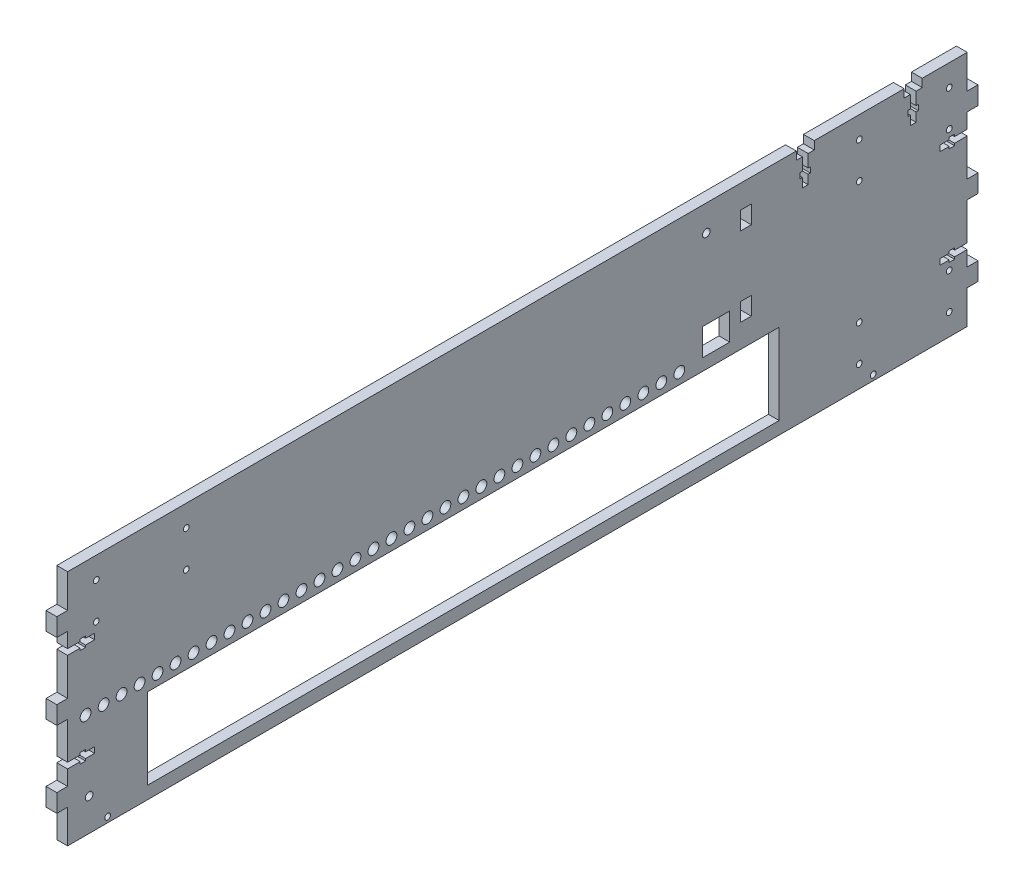
SolidWorks part; units mm, degrees
ref_plane "Front Plane" through (0, 0, 0) normal (0, 0, 1) x (1, 0, 0)
ref_plane "Top Plane" through (0, 0, 0) normal (0, 1, 0) x (1, 0, 0)
ref_plane "Right Plane" through (0, 0, 0) normal (1, 0, 0) x (0, 0, -1)
sketch "Sketch1" plane through (0, 0, 0) normal (1, 0, 0) x (0, 0, -1)
  line L1 (-250, -66) -> (250, -66)
  line L2 (-250, -66) -> (-250, 66)
  line L3 (-250, 66) -> (250, 66)
  line L4 (250, -66) -> (250, 66)
  line L5 (-250, -66) -> (250, 66) construction
  line L6 (-250, 66) -> (250, -66) construction
  point P0 (0, 0)
  dimension "D1" = 132
  dimension "D2" = 500
extrude "Boss-Extrude1" add sketch "Sketch1" along normal blind 6
sketch "Sketch4" plane through (0, 0, 250) normal (0, 0, 1) x (1, 0, 0)
  line L0 (0, 66) -> (0, -66) construction
  line L1 (0, 47.3321) -> (6, 47.3321)
  line L2 (0, 47.3321) -> (0, 37.3321)
  line L3 (0, 37.3321) -> (6, 37.3321)
  line L4 (6, 47.3321) -> (6, 37.3321)
  line L5 (6, 66) -> (6, -66) construction
  line L6 (0, 37.3321) -> (6, 37.3321) construction
  line L7 (0, -66) -> (0, 66) construction
  line L8 (6, 47.3321) -> (0, 47.3321) construction
  line L9 (0, -5) -> (6, -5) construction
  line L10 (0, -5) -> (6, -5)
  line L11 (0, -5) -> (0, 5)
  line L12 (0, 5) -> (6, 5)
  line L13 (6, -5) -> (6, 5)
  line L14 (6, -66) -> (6, 66) construction
  line L15 (6, 5) -> (0, 5) construction
  line L16 (6, -37.3321) -> (0, -37.3321) construction
  line L17 (0, -47.3321) -> (6, -47.3321)
  line L18 (0, -47.3321) -> (0, -37.3321)
  line L19 (0, -37.3321) -> (6, -37.3321)
  line L20 (6, -47.3321) -> (6, -37.3321)
  line L21 (0, -47.3321) -> (6, -47.3321) construction
extrude "Boss-Extrude2" add sketch "Sketch4" along normal blind 6
sketch "Sketch5" plane through (0, 0, 0) normal (-1, 0, 0) x (0, 0, 1)
  line L1 (250, 28.9321) -> (250, 25.7321) construction
  line L3 (250, 28.9321) -> (250, 25.7321) construction
  line L4 (250, -25.7321) -> (250, -28.9321) construction
  line L5 (250, -25.7321) -> (250, -28.9321) construction
  line L6 (250, 27.3321) -> (235, 27.3321) construction
  line L7 (250, -27.3321) -> (235, -27.3321) construction
  line L8 (250, -25.7321) -> (243, -25.7321)
  line L9 (250, 28.9321) -> (243, 28.9321)
  line L10 (250, -28.9321) -> (243, -28.9321)
  line L11 (250, 25.7321) -> (243, 25.7321)
  line L12 (250, -25.7321) -> (250, -28.9321)
  line L13 (235, -25.7321) -> (235, -28.9321)
  line L14 (250, 28.9321) -> (250, 25.7321)
  line L15 (235, 28.9321) -> (235, 25.7321)
  line L16 (240, 25.7321) -> (235, 25.7321)
  line L17 (243, 24.5321) -> (240, 24.5321)
  line L18 (243, 24.5321) -> (243, 25.7321)
  line L19 (243, 30.1321) -> (240, 30.1321)
  line L20 (240, 24.5321) -> (240, 25.7321)
  line L21 (243, 24.5321) -> (240, 30.1321) construction
  line L22 (243, 30.1321) -> (240, 24.5321) construction
  line L23 (243, -30.1321) -> (240, -30.1321)
  line L24 (243, -30.1321) -> (243, -28.9321)
  line L25 (243, -24.5321) -> (240, -24.5321)
  line L26 (240, -30.1321) -> (240, -28.9321)
  line L27 (243, -30.1321) -> (240, -24.5321) construction
  line L28 (243, -24.5321) -> (240, -30.1321) construction
  line L29 (250, 25.7321) -> (235, 25.7321) construction
  line L30 (243, 28.9321) -> (243, 30.1321)
  line L31 (240, 28.9321) -> (235, 28.9321)
  line L32 (250, 28.9321) -> (235, 28.9321) construction
  line L33 (240, 28.9321) -> (240, 30.1321)
  line L34 (240, -25.7321) -> (235, -25.7321)
  line L35 (250, -25.7321) -> (235, -25.7321) construction
  line L36 (240, -25.7321) -> (240, -24.5321)
  line L37 (240, -28.9321) -> (235, -28.9321)
  line L38 (250, -28.9321) -> (235, -28.9321) construction
  line L39 (243, -25.7321) -> (243, -24.5321)
  point P20 (241.5, 27.3321)
  point P25 (241.5, -27.3321)
  line M35 (250, -37.3321) -> (250, -5)
  line M39 (250, 5) -> (250, 37.3321)
  dimension "D3" = 1.6
  dimension "D4" = 7
  dimension "D5" = 3
  dimension "D6" = 5.6
  dimension "D1" = 15
  dimension "D7" = 7
  dimension "D8" = 3
  dimension "D9" = 5.6
  dimension "D2" = 1.6
extrude "Cut-Extrude3" cut sketch "Sketch5" against normal up to next contours L12 | L8 L39 L25 L36 L34 L13 L37 L26 L23 L24 L10 M35 | L33 L31 L15 L16 L20 L17 L18 L11 L9 L30 L19 M39 region at (0, -27.3321, 242.3696) region at (0, 27.3321, 242.3696)
sketch "Sketch6" plane through (0, 0, -250) normal (0, 0, -1) x (-1, 0, 0)
  line L0 (0, 47.3321) -> (0, 37.3321) construction
  line L1 (0, 37.3321) -> (-6, 37.3321) construction
  line L2 (-6, 37.3321) -> (-6, 47.3321) construction
  line L3 (-6, 47.3321) -> (0, 47.3321) construction
  line L4 (0, 5) -> (0, -5) construction
  line L5 (0, -5) -> (-6, -5) construction
  line L6 (-6, -5) -> (-6, 5) construction
  line L7 (-6, 5) -> (0, 5) construction
  line L8 (0, -37.3321) -> (0, -47.3321) construction
  line L9 (0, -47.3321) -> (-6, -47.3321) construction
  line L10 (-6, -47.3321) -> (-6, -37.3321) construction
  line L11 (-6, -37.3321) -> (0, -37.3321) construction
  line L12 (0, 47.3321) -> (0, 37.3321)
  line L13 (0, 37.3321) -> (-6, 37.3321)
  line L14 (-6, 37.3321) -> (-6, 47.3321)
  line L15 (-6, 47.3321) -> (0, 47.3321)
  line L16 (0, 5) -> (0, -5)
  line L17 (0, -5) -> (-6, -5)
  line L18 (-6, -5) -> (-6, 5)
  line L19 (-6, 5) -> (0, 5)
  line L20 (0, -37.3321) -> (0, -47.3321)
  line L21 (0, -47.3321) -> (-6, -47.3321)
  line L22 (-6, -47.3321) -> (-6, -37.3321)
  line L23 (-6, -37.3321) -> (0, -37.3321)
extrude "Boss-Extrude3" add sketch "Sketch6" along normal blind 6
sketch "Sketch7" plane through (0, 0, 0) normal (-1, 0, 0) x (0, 0, 1)
  line L0 (243, 25.7321) -> (250, 25.7321) construction
  line L2 (243, 25.7321) -> (243, 24.5321) construction
  line L3 (240, 24.5321) -> (243, 24.5321) construction
  line L4 (240, 25.7321) -> (240, 24.5321) construction
  line L5 (235, 25.7321) -> (240, 25.7321) construction
  line L6 (235, 25.7321) -> (235, 28.9321) construction
  line L7 (235, 28.9321) -> (240, 28.9321) construction
  line L8 (240, 30.1321) -> (240, 28.9321) construction
  line L9 (240, 30.1321) -> (243, 30.1321) construction
  line L10 (243, 30.1321) -> (243, 28.9321) construction
  line L11 (243, 28.9321) -> (250, 28.9321) construction
  line L12 (243, 25.7321) -> (250, 25.7321) construction
  line L13 (243, 25.7321) -> (243, 24.5321) construction
  line L14 (240, 24.5321) -> (243, 24.5321) construction
  line L15 (240, 25.7321) -> (240, 24.5321) construction
  line L16 (235, 25.7321) -> (240, 25.7321) construction
  line L17 (235, 25.7321) -> (235, 28.9321) construction
  line L18 (235, 28.9321) -> (240, 28.9321) construction
  line L19 (240, 30.1321) -> (240, 28.9321) construction
  line L20 (240, 30.1321) -> (243, 30.1321) construction
  line L21 (243, 30.1321) -> (243, 28.9321) construction
  line L22 (243, 28.9321) -> (250, 28.9321) construction
  line L23 (235, -28.9321) -> (240, -28.9321) construction
  line L24 (240, -28.9321) -> (240, -30.1321) construction
  line L25 (240, -30.1321) -> (243, -30.1321) construction
  line L26 (243, -28.9321) -> (243, -30.1321) construction
  line L27 (243, -28.9321) -> (250, -28.9321) construction
  line L28 (243, -25.7321) -> (250, -25.7321) construction
  line L29 (243, -24.5321) -> (243, -25.7321) construction
  line L30 (240, -24.5321) -> (243, -24.5321) construction
  line L31 (240, -24.5321) -> (240, -25.7321) construction
  line L32 (235, -25.7321) -> (240, -25.7321) construction
  line L33 (235, -28.9321) -> (235, -25.7321) construction
  line L34 (235, -28.9321) -> (240, -28.9321) construction
  line L35 (240, -28.9321) -> (240, -30.1321) construction
  line L36 (240, -30.1321) -> (243, -30.1321) construction
  line L37 (243, -28.9321) -> (243, -30.1321) construction
  line L38 (243, -28.9321) -> (250, -28.9321) construction
  line L39 (243, -25.7321) -> (250, -25.7321) construction
  line L40 (243, -24.5321) -> (243, -25.7321) construction
  line L41 (240, -24.5321) -> (243, -24.5321) construction
  line L42 (240, -24.5321) -> (240, -25.7321) construction
  line L43 (235, -25.7321) -> (240, -25.7321) construction
  line L44 (235, -28.9321) -> (235, -25.7321) construction
  line L45 (0, 0) -> (0, 57.5645) construction
  line L46 (-235, -28.9321) -> (-235, -25.7321)
  line L47 (-235, -25.7321) -> (-240, -25.7321)
  line L48 (-240, -24.5321) -> (-240, -25.7321)
  line L49 (-240, -24.5321) -> (-243, -24.5321)
  line L50 (-243, -24.5321) -> (-243, -25.7321)
  line L51 (-243, -25.7321) -> (-250, -25.7321)
  line L52 (-243, -28.9321) -> (-250, -28.9321)
  line L53 (-243, -28.9321) -> (-243, -30.1321)
  line L54 (-240, -30.1321) -> (-243, -30.1321)
  line L55 (-240, -28.9321) -> (-240, -30.1321)
  line L56 (-235, -28.9321) -> (-240, -28.9321)
  line L57 (-243, 28.9321) -> (-250, 28.9321)
  line L58 (-243, 30.1321) -> (-243, 28.9321)
  line L59 (-240, 30.1321) -> (-243, 30.1321)
  line L60 (-240, 30.1321) -> (-240, 28.9321)
  line L61 (-235, 28.9321) -> (-240, 28.9321)
  line L62 (-235, 25.7321) -> (-235, 28.9321)
  line L63 (-235, 25.7321) -> (-240, 25.7321)
  line L64 (-240, 25.7321) -> (-240, 24.5321)
  line L65 (-240, 24.5321) -> (-243, 24.5321)
  line L66 (-243, 25.7321) -> (-243, 24.5321)
  line L67 (-243, 25.7321) -> (-250, 25.7321)
  line L68 (-250, 28.9321) -> (-250, 25.7321)
  line L69 (-250, -25.7321) -> (-250, -28.9321)
extrude "Cut-Extrude4" cut sketch "Sketch7" against normal up to next
sketch "Sketch8" plane through (0, 0, 0) normal (-1, 0, 0) x (0, 0, 1)
  line L0 (205, -14.55) -> (-145, -14.55) construction
  line L1 (205, -14.55) -> (-145, -14.55) construction
  line L2 (205, -14.55) -> (205, -59) construction
  line L3 (205, -14.55) -> (205, -59) construction
  line L186 (-145, -14.55) -> (-145, -59) construction
  line L187 (-145, -59) -> (205, -59) construction
  line L188 (205.5, -14.05) -> (205.5, -59)
  line L189 (205.5, -14.05) -> (-145.5, -14.05)
  line L190 (-145.5, -14.05) -> (-145.5, -59)
  line L191 (-145.5, -59) -> (205.5, -59)
  dimension "D1" = 0.5
extrude "Cut-Extrude5" cut sketch "Sketch8" against normal up to next
sketch "Sketch11" plane through (6, 0, 0) normal (1, 0, 0) x (0, 0, -1)
  line L0 (130, 43) -> (130, 53) construction
  line L1 (130, 53) -> (124, 53) construction
  line L2 (124, 53) -> (124, 43) construction
  line L3 (124, 43) -> (130, 43) construction
  line L4 (130, -1) -> (130, 9) construction
  line L5 (130, 9) -> (124, 9) construction
  line L6 (124, 9) -> (124, -1) construction
  line L7 (124, -1) -> (130, -1) construction
  line L8 (130, 43) -> (130, 53)
  line L9 (130, 53) -> (124, 53)
  line L10 (124, 53) -> (124, 43)
  line L11 (124, 43) -> (130, 43)
  line L12 (130, -1) -> (130, 9)
  line L13 (130, 9) -> (124, 9)
  line L14 (124, 9) -> (124, -1)
  line L15 (124, -1) -> (130, -1)
extrude "Cut-Extrude8" cut sketch "Sketch11" against normal up to next
sketch "Sketch12" plane through (0, 0, 0) normal (-1, 0, 0) x (0, 0, 1)
  line L0 (-124, 53) -> (-124, 43) construction
  line L1 (-250, 66) -> (250, 66) construction
  circle A0 centre (-105, 51.5) radius 2.1
  dimension "D1" = 19
  dimension "D3" = 4.2
  dimension "D2" = 14.5
extrude "Cut-Extrude9" cut sketch "Sketch12" against normal up to next
sketch "Sketch13" plane through (0, 66, 0) normal (0, 1, 0) x (1, 0, 0)
  line L0 (6, 250) -> (6, -250) construction
  line L1 (0, 215) -> (6, 215)
  line L2 (0, 215) -> (0, 225)
  line L3 (0, 225) -> (6, 225)
  line L4 (6, 215) -> (6, 225)
  line L5 (0, 215) -> (6, 225) construction
  line L6 (0, 225) -> (6, 215) construction
  line L7 (6, 225) -> (0, 225) construction
  line L8 (6, 165) -> (0, 165) construction
  line L9 (0, 155) -> (6, 155)
  line L10 (0, 155) -> (0, 165)
  line L11 (0, 165) -> (6, 165)
  line L12 (6, 155) -> (6, 165)
  line L13 (0, 155) -> (6, 165) construction
  line L14 (0, 165) -> (6, 155) construction
  point P0 (3, 220)
  point P10 (3, 160)
extrude "Cut-Extrude10" cut sketch "Sketch13" against normal blind 4.5
sketch "Sketch14" plane through (0, 0, 0) normal (-1, 0, 0) x (0, 0, 1)
  circle A0 centre (240, -8) radius 3 construction
  circle A1 centre (240, -8) radius 3
  circle A2 centre (230, -8) radius 3
  circle A3 centre (220, -8) radius 3
  circle A4 centre (210, -8) radius 3
  circle A5 centre (200, -8) radius 3
  circle A6 centre (190, -8) radius 3
  circle A7 centre (180, -8) radius 3
  circle A8 centre (170, -8) radius 3
  circle A9 centre (160, -8) radius 3
  circle A10 centre (150, -8) radius 3
  circle A11 centre (140, -8) radius 3
  circle A12 centre (130, -8) radius 3
  circle A13 centre (120, -8) radius 3
  circle A14 centre (110, -8) radius 3
  circle A15 centre (100, -8) radius 3
  circle A16 centre (90, -8) radius 3
  circle A17 centre (80, -8) radius 3
  circle A18 centre (70, -8) radius 3
  circle A19 centre (60, -8) radius 3
  circle A20 centre (50, -8) radius 3
  circle A21 centre (40, -8) radius 3
  circle A22 centre (30, -8) radius 3
  circle A23 centre (20, -8) radius 3
  circle A24 centre (10, -8) radius 3
  circle A25 centre (0, -8) radius 3
  circle A26 centre (-10, -8) radius 3
  circle A27 centre (-20, -8) radius 3
  circle A28 centre (-30, -8) radius 3
  circle A29 centre (-40, -8) radius 3
  circle A30 centre (-50, -8) radius 3
  circle A31 centre (-60, -8) radius 3
  circle A32 centre (-70, -8) radius 3
  circle A33 centre (-80, -8) radius 3
  circle A34 centre (-90, -8) radius 3
  dimension "D1" = 34
extrude "Cut-Extrude11" cut sketch "Sketch14" against normal up to next (6 mm away)
sketch "Sketch15" plane through (6, 0, 0) normal (1, 0, 0) x (0, 0, -1)
  line L0 (160, 61.5) -> (160, 46.5) construction
  line L1 (155, 61.5) -> (165, 61.5) construction
  line L2 (220, 61.5) -> (220, 46.5) construction
  line L3 (215, 61.5) -> (225, 61.5) construction
  line L4 (160, 46.5) -> (220, 46.5) construction
  line L5 (190, 46.5) -> (190, 66) construction
  line L6 (215, 66) -> (165, 66) construction
  line L7 (158.4, 61.5) -> (158.4, 54.5)
  line L8 (161.6, 61.5) -> (161.6, 54.5)
  line L9 (158.4, 61.5) -> (161.6, 61.5)
  line L10 (158.4, 46.5) -> (161.6, 46.5)
  line L11 (161.6, 51.5) -> (162.8, 51.5)
  line L12 (157.2, 54.5) -> (158.4, 54.5)
  line L13 (157.2, 54.5) -> (157.2, 51.5)
  line L14 (157.2, 51.5) -> (158.4, 51.5)
  line L15 (162.8, 54.5) -> (162.8, 51.5)
  line L16 (157.2, 54.5) -> (162.8, 51.5) construction
  line L17 (157.2, 51.5) -> (162.8, 54.5) construction
  line L18 (161.6, 54.5) -> (162.8, 54.5)
  line L19 (158.4, 51.5) -> (158.4, 46.5)
  line L20 (158.4, 61.5) -> (158.4, 46.5) construction
  line L21 (161.6, 51.5) -> (161.6, 46.5)
  line L22 (161.6, 61.5) -> (161.6, 46.5) construction
  line L23 (222.8, 51.5) -> (217.2, 54.5) construction
  line L24 (222.8, 54.5) -> (217.2, 51.5) construction
  line L25 (220, 61.5) -> (220, 46.5) construction
  line L26 (218.4, 51.5) -> (218.4, 46.5)
  line L27 (221.6, 51.5) -> (221.6, 46.5)
  line L28 (218.4, 54.5) -> (217.2, 54.5)
  line L29 (217.2, 54.5) -> (217.2, 51.5)
  line L30 (222.8, 51.5) -> (221.6, 51.5)
  line L31 (222.8, 54.5) -> (222.8, 51.5)
  line L32 (222.8, 54.5) -> (221.6, 54.5)
  line L33 (218.4, 51.5) -> (217.2, 51.5)
  line L34 (221.6, 46.5) -> (218.4, 46.5)
  line L35 (221.6, 61.5) -> (218.4, 61.5)
  line L36 (218.4, 61.5) -> (218.4, 54.5)
  line L37 (221.6, 61.5) -> (221.6, 54.5)
  point P16 (160, 53)
  point P37 (220, 53)
  dimension "D3" = 15
  dimension "D4" = 7
  dimension "D5" = 3
  dimension "D6" = 5.6
  dimension "D1" = 1.6
  dimension "D2" = 1.6
extrude "Cut-Extrude12" cut sketch "Sketch15" against normal up to next
sketch "Sketch17" plane through (6, 0, 0) normal (1, 0, 0) x (0, 0, -1)
  circle A0 centre (-238, -48) radius 2.1 construction
  circle A1 centre (-238, -48) radius 2.1
extrude "Cut-Extrude14" cut sketch "Sketch17" against normal through all
sketch "Sketch18" plane through (6, 0, 0) normal (1, 0, 0) x (0, 0, -1)
  line L0 (-205.5, -59) -> (-250, -59) construction
  line L1 (-250, -47.3321) -> (-250, -66) construction
  line L2 (-227.75, -59) -> (-227.75, -66) construction
  line L3 (-250, -66) -> (250, -66) construction
  line L4 (145.5, -59) -> (250, -59) construction
  line L5 (250, -66) -> (250, -47.3321) construction
  line L6 (197.75, -59) -> (197.75, -66) construction
  circle A0 centre (-227.75, -63) radius 1.6
  circle A1 centre (197.75, -63) radius 1.6
  dimension "D1" = 3.2
  dimension "D2" = 3
extrude "Cut-Extrude15" cut sketch "Sketch18" against normal through all
sketch "Sketch19" plane through (6, 0, 0) normal (1, 0, 0) x (0, 0, -1)
  circle A1 centre (240, -34) radius 1.6
  circle A2 centre (240, -34) radius 1.6
  circle A3 centre (240, 54) radius 1.6
  circle A5 centre (240, 54) radius 1.6
  circle A7 centre (240, -54) radius 1.6
  circle A8 centre (240, -54) radius 1.6
  circle A11 centre (190, -54) radius 1.6
  circle A12 centre (190, -54) radius 1.6
  circle A15 centre (190, -34) radius 1.6
  circle A16 centre (190, -34) radius 1.6
  circle A24 centre (190, 34) radius 1.6
  circle A25 centre (190, 34) radius 1.6
  circle A30 centre (190, 54) radius 1.6
  circle A31 centre (190, 54) radius 1.6
  circle A32 centre (240, 34) radius 1.6
  circle A33 centre (240, 34) radius 1.6
  circle A56 centre (-184, 34) radius 1.6 construction
  circle A57 centre (-234, 34) radius 1.6 construction
  circle A58 centre (-184, 54) radius 1.6 construction
  circle A59 centre (-234, 54) radius 1.6 construction
  circle A60 centre (-184, 34) radius 1.6
  circle A61 centre (-234, 34) radius 1.6
  circle A62 centre (-184, 54) radius 1.6
  circle A63 centre (-234, 54) radius 1.6
  dimension "D1" = 0
  dimension "D2" = 0
  dimension "D5" = 0
  dimension "D7" = 0
  dimension "D9" = 0
  dimension "D12" = 0
  dimension "D15" = 0
  dimension "D16" = 0
extrude "Cut-Extrude16" cut sketch "Sketch19" against normal through all
sketch "Sketch20" plane through (6, 0, 0) normal (1, 0, 0) x (0, 0, -1)
  line L0 (-250, 22) -> (251, 22) construction
  line L1 (-250, 22) -> (251, 22) construction
  line L2 (-250, -22) -> (251, -22) construction
  line L3 (-250, -22) -> (251, -22) construction
  line L4 (118, 22) -> (118, -22) construction
  line L5 (124, 9) -> (124, -1) construction
  line L6 (118, 0) -> (103, 0) construction
  line L7 (118, 7.5) -> (103, 7.5)
  line L8 (118, -7.5) -> (103, -7.5)
  line L9 (118, 7.5) -> (118, -7.5)
  line L10 (103, 7.5) -> (103, -7.5)
  point P8 (124, 4)
  dimension "D1" = 6
  dimension "D2" = 15
  dimension "D3" = 7.5
  dimension "D4" = 7.5
extrude "Cut-Extrude17" cut sketch "Sketch20" against normal through all
